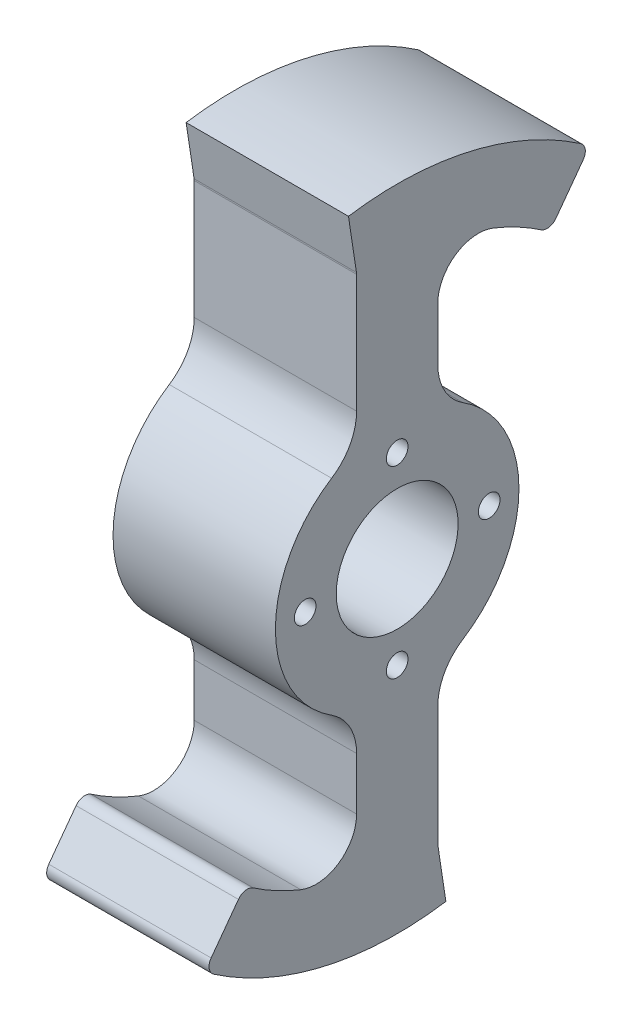
SolidWorks part; units mm, degrees
material "AISI Type A2 Tool Steel"
ref_plane "Front Plane" through (0, 0, 0) normal (0, 0, 1) x (1, 0, 0)
ref_plane "Top Plane" through (0, 0, 0) normal (0, 1, 0) x (1, 0, 0)
ref_plane "Right Plane" through (0, 0, 0) normal (1, 0, 0) x (0, 0, -1)
sketch "Sketch1" plane through (0, 0, 0) normal (1, 0, 0) x (0, 0, -1)
  line L0 (-9.525, 26.9408) -> (-9.525, 62.7816)
  line L1 (-9.525, 62.7816) -> (-11.43, 75.3379)
  line L2 (45.1897, 61.3542) -> (37.2511, 50.5758)
  line L3 (9.525, -26.9408) -> (9.525, -62.7816)
  line L4 (9.525, 47.0929) -> (9.525, 26.9408)
  line L5 (0, 28.575) -> (0, 117.6695) construction
  line L6 (45.1897, 61.3542) -> (134.5364, -4.4531) construction
  line L7 (9.525, -62.7816) -> (11.43, -75.3379)
  line L8 (-45.1897, -61.3542) -> (-37.2511, -50.5758)
  line L9 (-9.525, -47.0929) -> (-9.525, -26.9408)
  line L10 (0, -28.575) -> (0, -117.6695) construction
  line L11 (-45.1897, -61.3542) -> (-134.5364, 4.4531) construction
  circle A0 centre (0, 0) radius 28.575 construction
  circle A1 centre (0, 0) radius 14.3002
  arc A2 (-11.43, 75.3379) -> (45.1897, 61.3542) centre (0, 0) cw
  arc A3 (33.7835, 49.9778) -> (22.6219, 55.9228) centre (0, 0) ccw
  arc A4 (22.6219, 55.9228) -> (9.525, 47.0929) centre (19.05, 47.0929) ccw
  arc A5 (37.2511, 50.5758) -> (33.7835, 49.9778) centre (35.2059, 52.0822) cw
  arc A6 (11.43, -75.3379) -> (-45.1897, -61.3542) centre (0, 0) cw
  arc A7 (-33.7835, -49.9778) -> (-22.6219, -55.9228) centre (0, 0) ccw
  arc A8 (-22.6219, -55.9228) -> (-9.525, -47.0929) centre (-19.05, -47.0929) ccw
  arc A9 (-37.2511, -50.5758) -> (-33.7835, -49.9778) centre (-35.2059, -52.0822) cw
  arc A10 (-9.525, 26.9408) -> (-9.525, -26.9408) centre (0, 0) ccw
  arc A11 (9.525, 26.9408) -> (9.525, -26.9408) centre (0, 0) cw
  circle A12 centre (0, 0) radius 9.525
  point P18 (35.7752, 48.572)
  point P36 (0, 0)
  dimension "D1" = 57.15
  dimension "D2" = 28.6004
  dimension "D3" = 19.05
  dimension "D4" = 76.2
  dimension "D6" = 45
  dimension "D8" = 9.525
  dimension "D9" = 2.54
  dimension "D11" = 19.05
  dimension "D5" = 12.7
  dimension "D7" = 15.875
  dimension "D10" = 2
extrude "Boss-Extrude1" add sketch "Sketch1" along normal mid plane 38.1 contours A11 L4 A4 A3 A5 L2 A2 L1 L0 A10 L9 A8 A7 A9 L8 A6 L7 L3 A1 region at (0, 44.8612, 7.7532)
fillet "Fillet1" radius 2.54 4 edges at (0, -61.3542, 45.1897) (0, 61.3542, -45.1897) (0, -62.7816, -9.525) (0, 62.7816, 9.525)
fillet "Fillet2" radius 12.7 4 edges at (0, 26.9408, -9.525) (0, -26.9408, -9.525) (0, -26.9408, 9.525) (0, 26.9408, 9.525)
sketch "Sketch2" plane through (-19.05, 0, 0) normal (-1, 0, 0) x (0, 0, 1)
  circle A0 centre (0, 21.59) radius 2.54
  circle A1 centre (21.59, 0) radius 2.54
  circle A2 centre (0, -21.59) radius 2.54
  circle A3 centre (-21.59, 0) radius 2.54
  point P12 (0, 0)
  dimension "D1" = 5.08
  dimension "D2" = 21.59
  dimension "D3" = 4
extrude "Cut-Extrude1" cut sketch "Sketch2" against normal up to next
